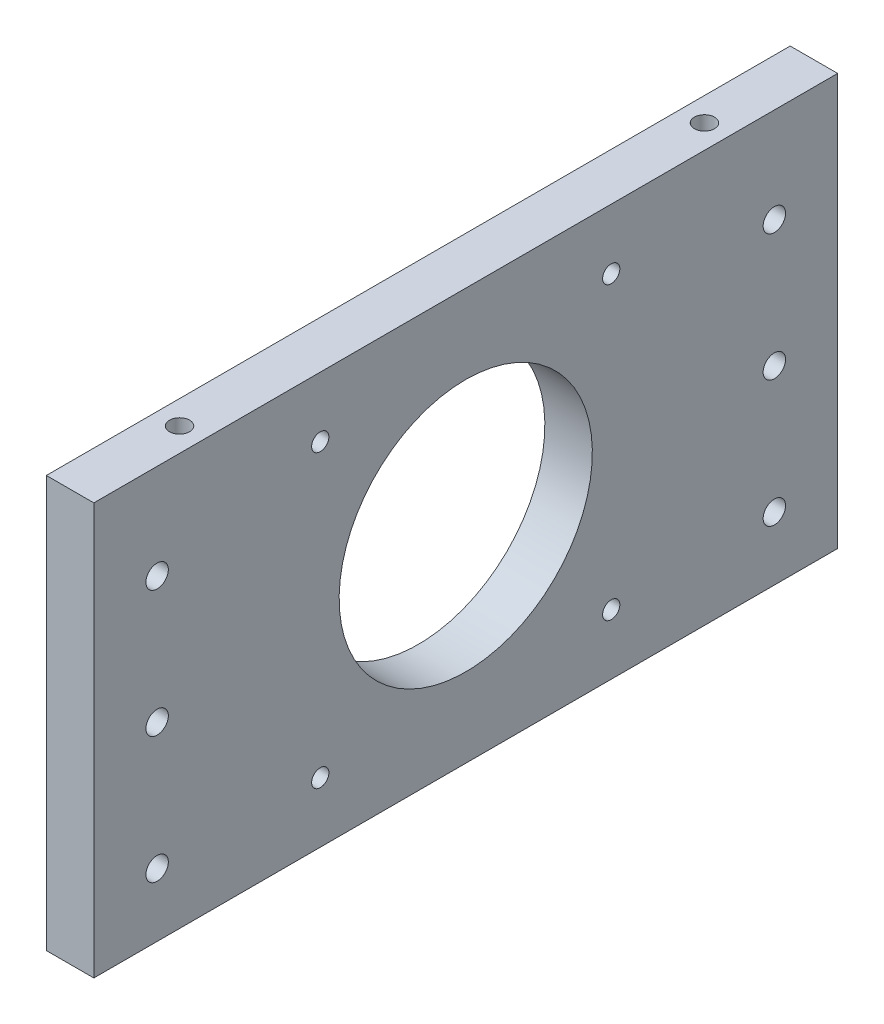
SolidWorks part; units mm, degrees
material "AISI 1015 Steel, Cold Drawn (SS)"
ref_plane "Front Plane" through (0, 0, 0) normal (0, 0, 1) x (1, 0, 0)
ref_plane "Top Plane" through (0, 0, 0) normal (0, 1, 0) x (1, 0, 0)
ref_plane "Right Plane" through (0, 0, 0) normal (1, 0, 0) x (0, 0, -1)
sketch "Sketch1" plane through (0, 0, 0) normal (0, 0, 1) x (1, 0, 0)
  line L1 (-4.7625, 41.275) -> (4.7625, 41.275)
  line L2 (-4.7625, 41.275) -> (-4.7625, -41.275)
  line L3 (-4.7625, -41.275) -> (4.7625, -41.275)
  line L4 (4.7625, 41.275) -> (4.7625, -41.275)
  line L5 (-4.7625, 41.275) -> (4.7625, -41.275) construction
  line L6 (-4.7625, -41.275) -> (4.7625, 41.275) construction
  point P0 (0, 0)
  dimension "D1" = 9.525
  dimension "D2" = 82.55
extrude "Boss-Extrude1" add sketch "Sketch1" along normal blind 149.225
hole_wizard "#8-32 Tapped Hole5" positions "Sketch3" profile "Sketch2" tap size "#8-32" standard "ANSI Inch" end condition through all
sketch "Sketch3" plane through (4.7625, 0, 0) normal (1, 0, 0) x (0, 0, -1)
  line L11 (-149.225, 41.275) -> (0, -41.275) construction
  line L14 (0, 41.275) -> (-149.225, -41.275) construction
  line L15 (-74.6125, -1000) -> (-74.6125, 49000) construction
  line L16 (-45.4267, 29.1858) -> (-74.6125, 0) construction
  circle A0 centre (-74.6125, 0) radius 41.275
  circle A1 centre (-74.6125, 0) radius 38.1
  point P91 (-45.4267, 29.1858)
  dimension "D1" = 3.175
  dimension "D3" = 76.2
  dimension "D4" = 82.55
  dimension "D2" = 45
sketch "Sketch2" plane through (4.7625, 29.1858, 45.4267) normal (0, 1, 0) x (0, 0, -1)
  line L0 (0, 0) -> (0, 9.525)
  line L1 (0, 9.525) -> (1.7272, 9.525)
  line L2 (1.7272, 9.525) -> (1.7272, 0)
  line L5 (1.7272, 0) -> (0, 0)
  line L11 (0, -6.35) -> (0, 107.95) construction
  dimension "Thread Major Dia." = 3.4544
  dimension "Thru Tap Drill Depth" = 9.525
hole_wizard "#8 Clearance Hole2" positions "Sketch5" profile "Sketch4" hole size "#8" standard "ANSI Inch" end condition through all
sketch "Sketch5" plane through (4.7625, 0, 0) normal (1, 0, 0) x (0, 0, -1)
  line L0 (-149.225, -41.275) -> (-149.225, 41.275) construction
  line L1 (-149.225, -41.275) -> (0, -41.275) construction
  line L2 (0, -41.275) -> (0, 41.275) construction
  point P0 (-136.525, 22.225)
  point P2 (-136.525, -3.175)
  point P4 (-136.525, -28.575)
  point P6 (-12.7, 22.225)
  point P8 (-12.7, -3.175)
  point P10 (-12.7, -28.575)
  dimension "D1" = 12.7
  dimension "D2" = 25.4
  dimension "D3" = 25.4
  dimension "D4" = 12.7
  dimension "D5" = 12.7
sketch "Sketch4" plane through (4.7625, 22.225, 136.525) normal (0, 1, 0) x (0, 0, -1)
  line L0 (0, 0) -> (0, 9.525)
  line L1 (0, 9.525) -> (2.2479, 9.525)
  line L2 (2.2479, 9.525) -> (2.2479, 0)
  line L5 (2.2479, 0) -> (0, 0)
  line L11 (0, -6.35) -> (0, 107.95) construction
  dimension "Thru Hole Dia." = 4.4958
  dimension "Thru Hole Depth" = 9.525
sketch "Sketch6" plane through (4.7625, 0, 0) normal (1, 0, 0) x (0, 0, -1)
  line L0 (-149.225, -41.275) -> (-74.6125, 0) construction
  line L1 (-74.6125, 0) -> (0, -41.275) construction
  circle A0 centre (-74.6125, 0) radius 25.4
  dimension "D1" = 50.8
extrude "Cut-Extrude1" cut sketch "Sketch6" against normal through all
pattern_circular "CirPattern1" count 4 over 360 about axis through (-4.7625, 0, 74.6125) along (1, 0, 0) of "#8-32 Tapped Hole5"
hole_wizard "#10-32 Tapped Hole1" positions "Sketch7" profile "Sketch8" tap size "#10-32" standard "ANSI Inch"
sketch "Sketch7" plane through (-79.375, 41.275, 74.6125) normal (0, 1, 0) x (0, 0, -1)
  line L0 (-52.6514, 84.1375) -> (-52.6514, 79.375) construction
  line L2 (-52.6514, 79.375) -> (-52.6514, 74.6125) construction
  line L6 (-74.6125, -52.6514) -> (-79.375, -52.6514) construction
  line L8 (-79.375, -52.6514) -> (-84.1375, -52.6514) construction
  circle A0 centre (0, 0) radius 95.25
  point P5 (-52.6514, 79.375)
  point P7 (-79.375, -52.6514)
  point P9 (-79.375, 52.6514)
  point P11 (-52.6514, -79.375)
  point P13 (52.6514, -79.375)
  point P15 (79.375, 52.6514)
  point P17 (79.375, -52.6514)
  point P19 (52.6514, 79.375)
  point P42 (0, 0)
  point P43 (0, 0)
  point P44 (0, 0)
  point P45 (0, 0)
  point P46 (0, 0)
  point P47 (0, 0)
sketch "Sketch8" plane through (-158.75, 41.275, 127.2639) normal (1, 0, 0) x (0, 0, 1)
  line L0 (0, 0) -> (0, 13.9133)
  line L1 (0, 13.9133) -> (2.0193, 12.7)
  line L2 (2.0193, 12.7) -> (2.0193, 0)
  line L3 (2.0193, 0) -> (0, 0)
  line L4 (0, 13.9133) -> (-2.0193, 12.7) construction
  line L5 (0, -6.35) -> (0, 107.95) construction
  dimension "Tap Drill Dia." = 4.0386
  dimension "Tap Drill Depth" = 12.7
  dimension "Drill Angle" = 118
cosmetic thread "Hole Thread1"
cosmetic thread "Hole Thread2"
hole_wizard "#10-32 Tapped Hole2" positions "Sketch9" profile "Sketch10" tap size "#10-32" standard "ANSI Inch"
sketch "Sketch9" plane through (-79.375, 41.275, 74.6125) normal (0, 1, 0) x (0, 0, 1)
  line L0 (-52.6514, 84.1375) -> (-52.6514, 79.375) construction
  line L2 (-52.6514, 79.375) -> (-52.6514, 74.6125) construction
  line L6 (-74.6125, -52.6514) -> (-79.375, -52.6514) construction
  line L8 (-79.375, -52.6514) -> (-84.1375, -52.6514) construction
  circle A0 centre (0, 0) radius 95.25
  point P5 (-52.6514, 79.375)
  point P7 (-79.375, -52.6514)
  point P9 (-79.375, 52.6514)
  point P11 (-52.6514, -79.375)
  point P13 (52.6514, -79.375)
  point P15 (79.375, 52.6514)
  point P17 (79.375, -52.6514)
  point P19 (52.6514, 79.375)
  point P42 (0, 0)
  point P43 (0, 0)
  point P44 (0, 0)
  point P45 (0, 0)
  point P46 (0, 0)
  point P47 (0, 0)
sketch "Sketch10" plane through (0, 41.275, 21.9611) normal (1, 0, 0) x (0, 0, 1)
  line L0 (0, 0) -> (0, 13.9133)
  line L1 (0, 13.9133) -> (2.0193, 12.7)
  line L2 (2.0193, 12.7) -> (2.0193, 0)
  line L3 (2.0193, 0) -> (0, 0)
  line L4 (0, 13.9133) -> (-2.0193, 12.7) construction
  line L5 (0, -6.35) -> (0, 107.95) construction
  dimension "Tap Drill Dia." = 4.0386
  dimension "Tap Drill Depth" = 12.7
  dimension "Drill Angle" = 118
